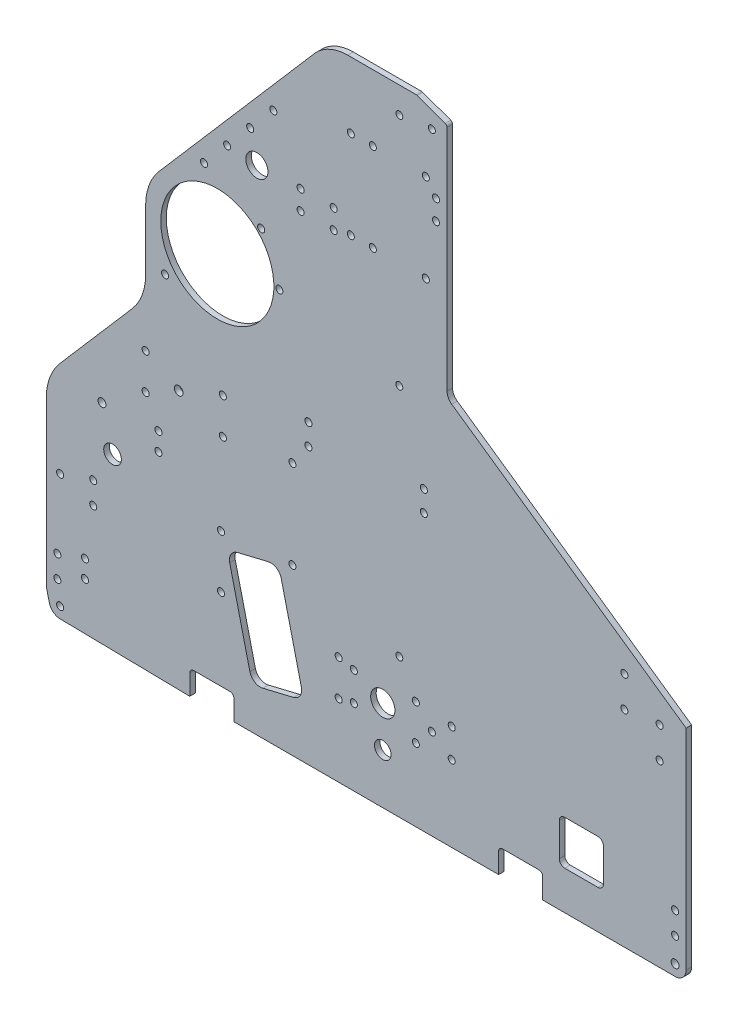
SolidWorks part; units mm, degrees
ref_plane "Front Plane" through (0, 0, 0) normal (0, 0, 1) x (1, 0, 0)
ref_plane "Top Plane" through (0, 0, 0) normal (0, 1, 0) x (1, 0, 0)
ref_plane "Right Plane" through (0, 0, 0) normal (1, 0, 0) x (0, 0, -1)
sketch "Sketch1" plane through (0, 0, 0) normal (0, 0, 1) x (1, 0, 0)
  line L0 (82.55, -20.32) -> (82.55, -6.35)
  line L2 (0, 0) -> (0, 157.48)
  line L4 (368.3, -20.32) -> (368.3, 106.68)
  line L5 (82.55, -6.35) -> (107.95, -6.35)
  line L6 (107.95, -6.35) -> (107.95, -20.32)
  line L7 (107.95, -20.32) -> (260.35, -20.32)
  line L8 (260.35, -20.32) -> (260.35, -6.35)
  line L9 (260.35, -6.35) -> (285.75, -6.35)
  line L10 (285.75, -6.35) -> (285.75, -20.32)
  line L11 (285.75, -20.32) -> (368.3, -20.32)
  line L12 (361.95, 12.7) -> (368.3, 12.7) construction
  line L13 (0, 0) -> (6.35, 0) construction
  line L14 (0.1896, -7.8901) -> (1.7771, -14.2401)
  line L15 (7.8295, -19.0491) -> (82.55, -20.32)
  line L16 (0, 0) -> (0, -6.35)
  line L17 (76.2, 128.905) -> (79.375, 128.905) construction
  line L18 (57.15, 118.5863) -> (101.6, 118.5862) construction
  line L19 (57.15, 118.5863) -> (57.15, 139.2238) construction
  line L20 (101.6, 118.5862) -> (101.6, 139.2237) construction
  line L21 (57.15, 139.2238) -> (101.6, 139.2237) construction
  line L22 (57.15, 118.5863) -> (101.6, 139.2237) construction
  line L23 (101.6, 118.5862) -> (57.15, 139.2238) construction
  line L25 (203.2, 59.805) -> (203.2, 194.805) construction
  line L26 (203.2, 194.805) -> (203.2, 329.805) construction
  line L27 (355.6, 332.105) -> (330.2, 332.105) construction
  line L28 (330.2, 332.105) -> (330.2, 217.805) construction
  line L29 (330.2, 217.805) -> (355.6, 217.805) construction
  line L30 (355.6, 217.805) -> (355.6, 332.105) construction
  line L31 (203.2, 344.805) -> (203.2, 194.805) construction
  line L32 (50.8, 332.105) -> (76.2, 332.105) construction
  line L33 (76.2, 332.105) -> (76.2, 217.805) construction
  line L34 (50.8, 217.805) -> (50.8, 332.105) construction
  line L35 (76.2, 217.805) -> (50.8, 217.805) construction
  line L36 (213.2, 344.805) -> (230.6638, 338.455)
  line L37 (203.2, 344.805) -> (161.925, 344.805)
  line L38 (203.2, 344.805) -> (213.2, 344.805)
  line L39 (348.5362, 344.805) -> (413.4623, 344.805)
  line L40 (348.5362, 344.805) -> (230.6638, 344.805) construction
  line L42 (161.925, 344.805) -> (0, 157.48)
  line L44 (230.6638, 338.455) -> (230.6638, 202.565)
  line L45 (230.6638, 202.565) -> (368.3, 106.68)
  line L46 (213.2, 344.805) -> (-141.0713, 344.805) construction
  circle A0 centre (6.35, 0) radius 2.032
  circle A1 centre (6.35, 12.7) radius 2.032
  circle A2 centre (361.95, 0) radius 2.032
  circle A3 centre (361.95, 12.7) radius 2.032
  arc A5 (1.7771, -14.2401) -> (7.8295, -19.0491) centre (7.9375, -12.7) ccw
  circle A6 centre (7.9375, -12.7) radius 2.032
  arc A7 (0, -6.35) -> (0.1896, -7.8901) centre (6.35, -6.35) ccw
  circle A8 centre (38.1, 78.105) radius 5.08
  circle A9 centre (76.2, 128.905) radius 2.54
  circle A10 centre (101.6, 118.5862) radius 2.032
  circle A11 centre (101.6, 139.2237) radius 2.032
  circle A12 centre (57.15, 139.2238) radius 2.032
  circle A13 centre (57.15, 118.5863) radius 2.032
  circle A15 centre (203.2, 59.805) radius 2
  circle A16 centre (203.2, 194.805) radius 2
  circle A17 centre (203.2, 329.805) radius 2
  circle A18 centre (63.5, 313.055) radius 2.032
  circle A20 centre (355.6, 332.105) radius 2.032
  circle A21 centre (330.2, 332.105) radius 2.032
  circle A22 centre (355.6, 217.805) radius 2.032
  circle A23 centre (330.2, 217.805) radius 2.032
  circle A24 centre (50.8, 332.105) radius 2.032
  circle A25 centre (76.2, 332.105) radius 2.032
  circle A26 centre (50.8, 217.805) radius 2.032
  circle A27 centre (76.2, 217.805) radius 2.032
  circle A28 centre (221.9319, 332.105) radius 2
  circle A29 centre (224.3138, 298.831) radius 2.032
  circle A30 centre (353.06, 100.7351) radius 2.032
  circle A31 centre (332.74, 115.9751) radius 2.032
  circle A32 centre (332.74, 98.1951) radius 2.032
  circle A33 centre (353.06, 82.9551) radius 2.032
  circle A34 centre (117.3562, 280.4276) radius 2.032
  circle A35 centre (104.0678, 265.0548) radius 2.032
  circle A36 centre (90.7795, 249.682) radius 2.032
  circle A38 centre (130.6445, 295.8004) radius 2.032
  circle A39 centre (68.326, 182.9237) radius 2.032
  circle A40 centre (224.3138, 287.401) radius 2.032
  point P82 (203.2, 344.805)
  point P83 (221.9319, 341.63)
  point P90 (368.3, 62.484)
  dimension "D6" = 4.064
  dimension "D10" = 6.35
  dimension "D11" = 4.064
  dimension "D17" = 38.1
  dimension "D27" = 4
  dimension "D31" = 4.064
  dimension "D32" = 41.275
  dimension "D36" = 4.064
  dimension "D47" = 39.624
  dimension "D48" = 4.064
  dimension "D25" = 5.08
  dimension "D26" = 4.064
  dimension "D52" = 4.064
  dimension "D65" = 4.064
  dimension "D69" = 10.16
  dimension "D2" = 127
  dimension "D3" = 13.97
  dimension "D4" = 25.4
  dimension "D5" = 152.4
  dimension "D7" = 12.7
  dimension "D8" = 6.35
  dimension "D9" = 20.32
  dimension "D12" = 12.7
  dimension "D13" = 1.5875
  dimension "D14" = 82.55
  dimension "D15" = 368.3
  dimension "D16" = 6.35
  dimension "D18" = 98.425
  dimension "D19" = 38.1
  dimension "D20" = 50.8
  dimension "D21" = 3.175
  dimension "D22" = 270
  dimension "D23" = 20.6375
  dimension "D24" = 44.45
  dimension "D28" = 135
  dimension "D29" = 12.7
  dimension "D30" = 15
  dimension "D33" = 63.5
  dimension "D34" = 27.4638
  dimension "D35" = 12.7
  dimension "D37" = 114.3
  dimension "D38" = 25.4
  dimension "D39" = 12.7
  dimension "D40" = 157.48
  dimension "D41" = 142.24
  dimension "D42" = 365.125
  dimension "D43" = 10
  dimension "D44" = 6.35
  dimension "D45" = 31.75
  dimension "D46" = 6.35
  dimension "D49" = 6.35
  dimension "D50" = 203.2
  dimension "D51" = 15.24
  dimension "D53" = 17.78
  dimension "D54" = 17.78
  dimension "D55" = 20.32
  dimension "D56" = 15.24
  dimension "D57" = 92.202
  dimension "D58" = 8.382
  dimension "D59" = 20.32
  dimension "D60" = 20.32
  dimension "D61" = 8.382
  dimension "D62" = 20.32
  dimension "D63" = 8.382
  dimension "D64" = 8.382
  dimension "D66" = 35.052
  dimension "D67" = 68.326
  dimension "D68" = 11.43
extrude "Boss-Extrude1" add sketch "Sketch1" along normal blind 3.175 contours L16 A7 L14 A5 L15 L2 A0 A1 A6 region at (171.4477, 119.565, 0)
fillet "Fillet1" radius 2.286 4 edges at (285.75, -6.35, 1.5875) (107.95, -6.35, 1.5875) (260.35, -6.35, 1.5875) (82.55, -6.35, 1.5875)
fillet "Fillet2" radius 6.35 1 edges at (230.6638, 202.565, 1.5875)
sketch "Sketch2" plane through (0, 0, 0) normal (0, 0, -1) x (-1, 0, 0)
  circle A0 centre (-100.5528, 71.086) radius 2.032 construction
  circle A1 centre (-100.5528, 40.606) radius 2.032 construction
  circle A2 centre (-22.225, 18.2025) radius 2.032 construction
  circle A3 centre (-22.225, 8.0425) radius 2.032 construction
  circle A4 centre (-100.5528, 71.086) radius 2.032
  circle A5 centre (-100.5528, 40.606) radius 2.032
  circle A6 centre (-22.225, 18.2025) radius 2.032
  circle A7 centre (-22.225, 8.0425) radius 2.032
extrude "Cut-Extrude1" cut sketch "Sketch2" against normal through all
fillet "Fillet3" radius 1.5875 2 edges at (230.6638, 338.455, 1.5875) (213.2, 344.805, 1.5875)
sketch "Sketch3" plane through (0, 0, 3.175) normal (0, 0, 1) x (1, 0, 0)
  line L0 (132.9524, 63.2646) -> (132.7215, 64.2281) construction
  line L1 (128.3814, 66.8897) -> (110.6828, 62.6472) construction
  line L2 (114.5132, 58.4237) -> (126.8822, 61.3887) construction
  line L3 (108.0212, 58.3071) -> (108.2522, 57.3436) construction
  line L4 (131.2006, 57.703) -> (140.0164, 20.9265) construction
  line L5 (144.0993, 16.7636) -> (132.9524, 63.2646) construction
  line L6 (108.2522, 57.3436) -> (119.3991, 10.8426) construction
  line L7 (121.1509, 16.4042) -> (112.3351, 53.1807) construction
  line L8 (119.3991, 10.8426) -> (119.6301, 9.8791) construction
  line L9 (144.3303, 15.8001) -> (144.0993, 16.7636) construction
  line L10 (137.8383, 15.6835) -> (125.4694, 12.7185) construction
  line L11 (123.9701, 7.2175) -> (141.6687, 11.4601) construction
  line L12 (132.9524, 63.2646) -> (132.7215, 64.2281)
  line L13 (128.3814, 66.8897) -> (110.6828, 62.6472)
  line L14 (114.5132, 58.4237) -> (126.8822, 61.3887)
  line L15 (108.0212, 58.3071) -> (108.2522, 57.3436)
  line L16 (131.2006, 57.703) -> (140.0164, 20.9265)
  line L17 (144.0993, 16.7636) -> (132.9524, 63.2646)
  line L18 (108.2522, 57.3436) -> (119.3991, 10.8426)
  line L19 (121.1509, 16.4042) -> (112.3351, 53.1807)
  line L20 (119.3991, 10.8426) -> (119.6301, 9.8791)
  line L21 (144.3303, 15.8001) -> (144.0993, 16.7636)
  line L22 (137.8383, 15.6835) -> (125.4694, 12.7185)
  line L23 (123.9701, 7.2175) -> (141.6687, 11.4601)
  line L24 (127.7894, 69.3598) -> (110.0908, 65.1172)
  line L25 (105.5512, 57.715) -> (105.7822, 56.7515)
  line L26 (105.7822, 56.7515) -> (116.9291, 10.2505)
  line L27 (116.9291, 10.2505) -> (117.16, 9.287)
  line L28 (124.5622, 4.7475) -> (142.2608, 8.99)
  line L29 (146.8003, 16.3922) -> (146.5694, 17.3557)
  line L30 (146.5694, 17.3557) -> (135.4225, 63.8567)
  line L31 (135.4225, 63.8567) -> (135.1915, 64.8202)
  line L32 (14.605, -0.1369) -> (103.7278, 32.3011) construction
  line L33 (14.605, -0.1369) -> (103.7278, 32.3011)
  line L34 (0, -6.35) -> (0, 157.48) construction
  line L35 (-39.6666, 74.7152) -> (103.7278, 126.9065) construction
  line L36 (26.9875, 46.9531) -> (26.9875, 59.6531) construction
  line L37 (107.95, -20.32) -> (260.35, -20.32) construction
  line L38 (64.5259, 92.5258) -> (64.5259, 102.9405) construction
  arc A0 (132.7215, 64.2281) -> (128.6308, 66.9403) centre (129.2206, 63.3889) ccw construction
  arc A1 (110.6828, 62.6472) -> (110.4377, 62.5791) centre (111.522, 59.1463) ccw construction
  arc A2 (128.6308, 66.9403) -> (128.3814, 66.8897) centre (129.2206, 63.3889) ccw construction
  arc A3 (110.4377, 62.5791) -> (108.0212, 58.3071) centre (111.522, 59.1463) ccw construction
  arc A4 (119.6301, 9.8791) -> (123.7207, 7.1669) centre (123.1309, 10.7183) ccw construction
  arc A5 (141.9139, 11.5281) -> (144.3303, 15.8001) centre (140.8295, 14.9609) ccw construction
  arc A6 (141.6687, 11.4601) -> (141.9139, 11.5281) centre (140.8295, 14.9609) ccw construction
  arc A7 (123.7207, 7.1669) -> (123.9701, 7.2175) centre (123.1309, 10.7183) ccw construction
  arc A8 (132.7215, 64.2281) -> (128.6308, 66.9403) centre (129.2206, 63.3889) ccw
  arc A9 (110.6828, 62.6472) -> (110.4377, 62.5791) centre (111.522, 59.1463) ccw
  arc A10 (128.6308, 66.9403) -> (128.3814, 66.8897) centre (129.2206, 63.3889) ccw
  arc A11 (110.4377, 62.5791) -> (108.0212, 58.3071) centre (111.522, 59.1463) ccw
  arc A12 (119.6301, 9.8791) -> (123.7207, 7.1669) centre (123.1309, 10.7183) ccw
  arc A13 (141.9139, 11.5281) -> (144.3303, 15.8001) centre (140.8295, 14.9609) ccw
  arc A14 (141.6687, 11.4601) -> (141.9139, 11.5281) centre (140.8295, 14.9609) ccw
  arc A15 (123.7207, 7.1669) -> (123.9701, 7.2175) centre (123.1309, 10.7183) ccw
  arc A16 (110.0908, 65.1172) -> (109.6726, 65.0012) centre (111.522, 59.1463) ccw
  arc A17 (109.6726, 65.0012) -> (105.5512, 57.715) centre (111.522, 59.1463) ccw
  arc A18 (117.16, 9.287) -> (124.1369, 4.6613) centre (123.1309, 10.7183) ccw
  arc A19 (124.1369, 4.6613) -> (124.5622, 4.7475) centre (123.1309, 10.7183) ccw
  arc A20 (142.2608, 8.99) -> (142.6789, 9.1061) centre (140.8295, 14.9609) ccw
  arc A21 (142.6789, 9.1061) -> (146.8003, 16.3922) centre (140.8295, 14.9609) ccw
  arc A22 (135.1915, 64.8202) -> (128.2147, 69.446) centre (129.2206, 63.3889) ccw
  arc A23 (128.2147, 69.446) -> (127.7894, 69.3598) centre (129.2206, 63.3889) ccw
  circle A26 centre (134.1438, 208.2281) radius 2.032 construction
  circle A33 centre (26.9875, 46.9531) radius 2.032
  circle A34 centre (26.9875, 59.6531) radius 2.032
  circle A35 centre (7.9375, 53.3031) radius 2.032
  circle A37 centre (32.0306, 100.8109) radius 31.75 construction
  circle A38 centre (32.0306, 100.8109) radius 2.286
  circle A39 centre (123.682, 233.4851) radius 2.032 construction
  circle A40 centre (64.5259, 102.9405) radius 2.032
  circle A41 centre (64.5259, 92.5258) radius 2.032
  circle A42 centre (134.1438, 208.2281) radius 2.032
  circle A43 centre (123.682, 233.4851) radius 2.032
  ellipse E0 centre (124.5974, 48.8487) end of major axis (128.5376, 61.3578) minor radius 6 (131.2006, 57.703) -> (126.8822, 61.3887) ccw construction
  ellipse E1 centre (122.2349, 48.2824) end of major axis (113.0518, 57.6456) minor radius 6 (114.5132, 58.4237) -> (112.3351, 53.1807) ccw construction
  ellipse E2 centre (127.7541, 25.2585) end of major axis (131.6942, 37.7675) minor radius 6 (121.1509, 16.4042) -> (125.4694, 12.7185) ccw construction
  ellipse E3 centre (130.1166, 25.8248) end of major axis (139.2998, 16.4616) minor radius 6 (137.8383, 15.6835) -> (140.0164, 20.9265) ccw construction
  ellipse E4 centre (124.5974, 48.8487) end of major axis (120.6573, 36.3397) minor radius 6 (131.2006, 57.703) -> (126.8822, 61.3887) ccw
  ellipse E5 centre (122.2349, 48.2824) end of major axis (131.4181, 38.9192) minor radius 6 (114.5132, 58.4237) -> (112.3351, 53.1807) ccw
  ellipse E6 centre (127.7541, 25.2585) end of major axis (131.6942, 37.7675) minor radius 6 (121.1509, 16.4042) -> (125.4694, 12.7185) ccw
  ellipse E7 centre (130.1166, 25.8248) end of major axis (139.2998, 16.4616) minor radius 6 (137.8383, 15.6835) -> (140.0164, 20.9265) ccw
  point P93 (26.9875, 53.3031)
  point P115 (32.0306, 100.8109)
  dimension "D3" = 63.5
  dimension "D4" = 4.572
  dimension "D8" = 4.064
  dimension "D2" = 88.9
  dimension "D5" = 7.9375
  dimension "D6" = 19.05
  dimension "D7" = 73.6231
  dimension "D9" = 12.7
  dimension "D10" = 10.4147
  dimension "D11" = 37.5384
  dimension "D12" = 45.5727
  dimension "D1" = 2.54
extrude "Cut-Extrude2" cut sketch "Sketch3" against normal through all contours A22 A23 L24 A16 A17 L25 L26 L27 A18 A19 L28 A20 A21 L29 L30 L31 A15 A12 L20 L18 L15 A11 A9 L13 A10 A8 L12 L17 L21 A13 A14 L23 | A12 A15 L23 A14 A13 L21 L17 L12 A8 A10 L13 A9 A11 L15 L18 L20 E7 L22 E6 L19 E5 L14 E4 L16 | L22 E7 L16 E4 L14 E5 L19 E6 | A38 | A41 | A40 | A35 | A34 | A33 | A43 | A42 region at (137.844, 39.8506, 3.175) region at (126.1758, 37.0536, 3.175) region at (128.1544, 68.6507, 3.175) region at (32.0306, 100.8109, 3.175) region at (64.5259, 102.9405, 3.175) region at (64.5259, 92.5258, 3.175)
sketch "Sketch4" plane through (0, 0, 3.175) normal (0, 0, 1) x (1, 0, 0)
  line L0 (57.15, 139.2238) -> (101.6, 139.2237) construction
  line L1 (168.275, 21.4312) -> (212.725, 21.4312) construction
  line L2 (168.275, 21.4312) -> (168.275, 42.0687) construction
  line L3 (168.275, 42.0687) -> (212.725, 42.0687) construction
  line L4 (212.725, 21.4312) -> (212.725, 42.0687) construction
  line L5 (168.275, 21.4312) -> (212.725, 42.0687) construction
  line L6 (168.275, 42.0687) -> (212.725, 21.4312) construction
  line L7 (57.15, 118.5863) -> (57.15, 139.2238) construction
  line L8 (107.95, -20.32) -> (260.35, -20.32) construction
  line L9 (193.675, 31.75) -> (177.005, 31.75) construction
  line L10 (190.5, 31.75) -> (193.675, 31.75) construction
  line L11 (6.35, 12.7) -> (361.95, 12.7) construction
  line L12 (107.95, -6.35) -> (107.95, -20.32) construction
  line L13 (193.675, 31.75) -> (220.6625, 31.75) construction
  line L14 (177.005, 23.4569) -> (177.005, 40.0431) construction
  line L15 (213.2, 44.805) -> (193.2, 44.805) construction
  line L16 (213.2, 44.805) -> (213.2, 344.805) construction
  line L17 (213.2, 344.805) -> (193.2, 344.805) construction
  line L18 (193.2, 44.805) -> (193.2, 344.805) construction
  line L19 (213.2, 44.805) -> (193.2, 344.805) construction
  line L20 (213.2, 344.805) -> (193.2, 44.805) construction
  line L21 (226.9319, 332.105) -> (226.9319, 31.75) construction
  line L22 (237.33, 40.0431) -> (233.3612, 40.0431) construction
  line L23 (237.33, 23.4569) -> (233.3612, 23.4569) construction
  circle A0 centre (168.275, 42.0687) radius 2.032
  circle A1 centre (212.725, 42.0687) radius 2.032
  circle A2 centre (212.725, 21.4312) radius 2.032
  circle A3 centre (168.275, 21.4312) radius 2.032
  circle A4 centre (193.675, 31.75) radius 6.985
  circle A7 centre (220.6625, 31.75) radius 14.2875 construction
  circle A8 centre (193.675, 31.75) radius 12.7 construction
  circle A9 centre (177.005, 40.0431) radius 2.032
  circle A10 centre (177.005, 23.4569) radius 2.032
  circle A11 centre (237.33, 40.0431) radius 2.032 construction
  circle A12 centre (237.33, 23.4569) radius 2.032 construction
  circle A13 centre (193.675, 8.4667) radius 4.7625
  circle A14 centre (221.9319, 31.75) radius 2.032
  circle A15 centre (221.9319, 31.75) radius 5 construction
  circle A16 centre (221.9319, 332.105) radius 5 construction
  circle A17 centre (233.3612, 23.4569) radius 2.032
  circle A18 centre (233.3612, 40.0431) radius 2.032
  point P0 (190.5, 31.75)
  point P26 (203.2, 194.805)
  point P38 (177.005, 31.75)
  dimension "D1" = 4.064
  dimension "D4" = 13.97
  dimension "D7" = 9.525
  dimension "D10" = 25.4
  dimension "D11" = 28.575
  dimension "D16" = 10
  dimension "D17" = 4.064
  dimension "D18" = 10
  dimension "D2" = 52.07
  dimension "D3" = 3.175
  dimension "D5" = 82.55
  dimension "D6" = 26.9875
  dimension "D8" = 20
  dimension "D9" = 300
  dimension "D12" = 16.67
  dimension "D13" = 16.5862
  dimension "D14" = 60.325
  dimension "D15" = 23.2833
  dimension "D19" = 3.9688
extrude "Cut-Extrude3" cut sketch "Sketch4" against normal through all
sketch "Sketch5" plane through (0, 0, 0) normal (0, 0, -1) x (-1, 0, 0)
  line L0 (-57.15, 223.5947) -> (-57.15, 165.3337)
  line L1 (-161.925, 344.805) -> (-52.7201, 218.4699) construction
  line L2 (-57.15, 165.3337) -> (0, 99.219)
  line L3 (0, -6.35) -> (0, 157.48) construction
  line L5 (-50.4199, 215.8089) -> (0, 157.48) construction
  line L6 (-57.15, 223.5947) -> (0, 157.48)
  line L7 (0, 157.48) -> (0, 99.219)
  line L8 (-361.95, -13.97) -> (-368.3, -13.97) construction
  line L9 (-361.95, -13.97) -> (-361.95, -20.32) construction
  line L10 (-285.75, -20.32) -> (-368.3, -20.32) construction
  line L11 (-368.3, -20.32) -> (-368.3, 106.68) construction
  circle A0 centre (-98.425, 208.2281) radius 32.5437
  circle A2 centre (-361.95, -13.97) radius 2.286
  dimension "D3" = 65.0875
  dimension "D7" = 4.572
  dimension "D1" = 38.1
  dimension "D2" = 57.15
  dimension "D4" = 41.275
  dimension "D5" = 41.275
  dimension "D6" = 6.35
extrude "Cut-Extrude5" cut sketch "Sketch5" against normal through all contours A0 | L7 L6 L0 L2 | A2 region at (28.575, 161.4068, 0) region at (98.425, 208.2281, 0)
fillet "Fillet4" radius 31.75 3 edges at (0, 99.219, 1.5875) (57.15, 165.3337, 1.5875) (57.15, 223.5947, 1.5875)
sketch "Sketch6" plane through (0, 0, 3.175) normal (0, 0, 1) x (1, 0, 0)
  line L0 (285.75, -20.32) -> (368.3, -20.32) construction
  line L1 (298.45, 27.305) -> (317.5, 27.305)
  line L2 (295.275, 24.13) -> (295.275, 5.08)
  line L3 (298.45, 1.905) -> (317.5, 1.905)
  line L4 (320.675, 24.13) -> (320.675, 5.08)
  line L5 (295.275, 27.305) -> (320.675, 1.905) construction
  line L6 (295.275, 1.905) -> (320.675, 27.305) construction
  line L7 (368.3, -20.32) -> (368.3, 106.68) construction
  arc A0 (295.275, 5.08) -> (298.45, 1.905) centre (298.45, 5.08) ccw
  arc A1 (317.5, 1.905) -> (320.675, 5.08) centre (317.5, 5.08) ccw
  arc A2 (317.5, 27.305) -> (320.675, 24.13) centre (317.5, 24.13) cw
  arc A3 (298.45, 27.305) -> (295.275, 24.13) centre (298.45, 24.13) ccw
  point P0 (307.975, 14.605)
  dimension "D2" = 3.175
  dimension "D1" = 25.4
  dimension "D3" = 22.225
  dimension "D4" = 47.625
extrude "Cut-Extrude6" cut sketch "Sketch6" against normal through all
fillet "Fillet5" radius 25.4 1 edges at (161.925, 344.805, 1.5875)
sketch "Sketch8" plane through (0, 0, 0) normal (0, 0, -1) x (-1, 0, 0)
  line L0 (-230.6638, 337.343) -> (-230.6638, 205.8802) construction
  line L1 (-230.6638, 255.905) -> (-175.26, 255.905) construction
  line L2 (-175.26, 255.905) -> (-175.26, 306.705) construction
  line L3 (-175.26, 306.705) -> (-230.6638, 306.705) construction
  line L4 (-173.5432, 344.805) -> (-212.9203, 344.805) construction
  circle A8 centre (-187.96, 306.705) radius 2.032
  circle A11 centre (-205.74, 306.705) radius 2.032
  circle A13 centre (-205.74, 255.905) radius 2.032
  circle A14 centre (-187.96, 255.905) radius 2.032
  circle A16 centre (-218.44, 306.705) radius 2.032
  circle A17 centre (-175.26, 306.705) radius 2.032
  circle A18 centre (-175.26, 255.905) radius 2.032
  circle A19 centre (-218.44, 255.905) radius 2.032
  circle A20 centre (-218.44, 306.705) radius 3.9687
  circle A21 centre (-205.74, 306.705) radius 3.9687
  circle A22 centre (-175.26, 306.705) radius 3.9687
  circle A23 centre (-218.44, 255.905) radius 3.9688
  circle A24 centre (-205.74, 255.905) radius 3.9688
  circle A25 centre (-187.96, 255.905) radius 3.9688
  circle A26 centre (-175.26, 255.905) radius 3.9688
  circle A27 centre (-187.96, 306.705) radius 3.9687
  point P1 (0, 0)
  point P3 (0, 0)
  point P6 (0, 0)
  point P7 (0, 0)
  point P9 (0, 0)
  point P11 (0, 0)
  point P12 (0, 0)
  point P18 (0, 0)
  point P37 (0, 0)
  dimension "D1" = 7.9375
  dimension "D7" = 4.064
  dimension "D2" = 12.2237
  dimension "D3" = 12.7
  dimension "D4" = 17.78
  dimension "D5" = 12.7
  dimension "D6" = 88.9
  dimension "D8" = 38.1
  dimension "D9" = 17.78
  dimension "D10" = 12.7
  dimension "D11" = 55.4037
  dimension "D12" = 12.7
extrude "Cut-Extrude7" cut sketch "Sketch8" against normal through all contours A16 | A17 | A18 | A19 | A8 | A14 region at (218.44, 306.705, 0) region at (175.26, 306.705, 0) region at (175.26, 255.905, 0) region at (218.44, 255.905, 0)
sketch "Sketch10" plane through (0, 0, 3.175) normal (0, 0, 1) x (1, 0, 0)
  circle A4 centre (141.6425, 74.6844) radius 2.032 construction
  circle A5 centre (141.6425, 125.4844) radius 2.032 construction
  circle A6 centre (141.6425, 74.6844) radius 2.032
  circle A7 centre (141.6425, 125.4844) radius 2.032
extrude "Cut-Extrude8" cut sketch "Sketch10" against normal through all
fillet "Fillet6" radius 6.35 1 edges at (368.3, -20.32, 1.5875)
sketch "Sketch11" plane through (0, 0, 3.175) normal (0, 0, 1) x (1, 0, 0)
  ellipse E4 centre (150.8814, 138.43) end of major axis (150.8814, 140.462) minor radius 2.032
  ellipse E5 centre (150.8814, 150.495) end of major axis (150.8814, 152.527) minor radius 2.032
  ellipse E6 centre (217.3024, 150.495) end of major axis (217.3024, 152.527) minor radius 2.032
  ellipse E7 centre (217.3024, 138.43) end of major axis (217.3024, 140.462) minor radius 2.032
extrude "Cut-Extrude9" cut sketch "Sketch11" against normal through all
sketch "Sketch12" plane through (0, 0, 0) normal (0, 0, -1) x (-1, 0, 0)
  line L0 (-173.5432, 344.805) -> (-212.9203, 344.805) construction
  circle A0 centre (-165.4175, 264.635) radius 2.032
  circle A1 centre (-203.2, 329.805) radius 2 construction
  circle A2 centre (-165.4175, 253.5225) radius 2.032
  circle A3 centre (-146.3675, 253.5225) radius 2.032
  circle A4 centre (-146.3675, 264.635) radius 2.032
  dimension "D1" = 80.17
  dimension "D2" = 4.064
  dimension "D3" = 37.7825
  dimension "D4" = 11.1125
  dimension "D5" = 19.05
extrude "Cut-Extrude10" cut sketch "Sketch12" against normal through all
sketch "Sketch13" plane through (0, 0, 0) normal (0, 0, -1) x (-1, 0, 0)
  line L0 (-190.2532, 261.8265) -> (-167.7107, 270.5564)
  line L1 (-140.0175, 264.635) -> (-140.0175, 253.5225)
  line L2 (-166.0849, 247.2077) -> (-188.6274, 249.5902)
  line L3 (-165.4175, 247.1725) -> (-146.3675, 247.1725)
  line L4 (-165.4175, 270.985) -> (-146.3675, 270.985)
  circle A0 centre (-146.3675, 264.635) radius 2.032 construction
  circle A1 centre (-146.3675, 253.5225) radius 2.032 construction
  circle A2 centre (-165.4175, 253.5225) radius 2.032 construction
  circle A3 centre (-165.4175, 264.635) radius 2.032 construction
  circle A4 centre (-175.26, 255.905) radius 2.032 construction
  circle A5 centre (-187.96, 255.905) radius 2.032 construction
  circle A6 centre (-146.3675, 264.635) radius 2.032
  circle A7 centre (-146.3675, 253.5225) radius 2.032
  circle A8 centre (-165.4175, 253.5225) radius 2.032
  circle A9 centre (-165.4175, 264.635) radius 2.032
  circle A10 centre (-175.26, 255.905) radius 2.032
  circle A11 centre (-187.96, 255.905) radius 2.032
  arc A12 (-188.6274, 249.5902) -> (-190.2532, 261.8265) centre (-187.96, 255.905) cw
  arc A13 (-167.7107, 270.5564) -> (-165.4175, 270.985) centre (-165.4175, 264.635) cw
  arc A14 (-166.0849, 247.2077) -> (-165.4175, 247.1725) centre (-165.4175, 253.5225) ccw
  arc A15 (-146.3675, 247.1725) -> (-140.0175, 253.5225) centre (-146.3675, 253.5225) ccw
  arc A16 (-146.3675, 270.985) -> (-140.0175, 264.635) centre (-146.3675, 264.635) cw
  dimension "D1" = 6.35
extrude "Boss-Extrude2" [suppressed] add sketch "Sketch13" along normal blind 6.35 separate body
sketch "Sketch14" plane through (0, 0, 0) normal (0, 0, -1) x (-1, 0, 0)
  line L0 (-130.6445, 295.8004) -> (-121.1847, 263.6885) construction
  line L1 (-121.1847, 263.6885) -> (-90.7795, 249.682) construction
  line L2 (-154.3272, 336.0154) -> (-64.88, 232.5373) construction
  line L4 (-118.517, 269.4796) -> (-115.3937, 261.0208) construction
  line L5 (-118.517, 269.4796) -> (-126.9758, 266.3562) construction
  line L6 (-126.9758, 266.3562) -> (-123.8524, 257.8974) construction
  line L7 (-115.3937, 261.0208) -> (-123.8524, 257.8974) construction
  line L8 (-118.517, 269.4796) -> (-123.8524, 257.8974) construction
  line L9 (-126.9758, 266.3562) -> (-115.3937, 261.0208) construction
  circle A0 centre (-121.1847, 263.6885) radius 6.376
  dimension "D1" = 22.225
  dimension "D2" = 9.017
extrude "Cut-Extrude11" cut sketch "Sketch14" against normal through all
